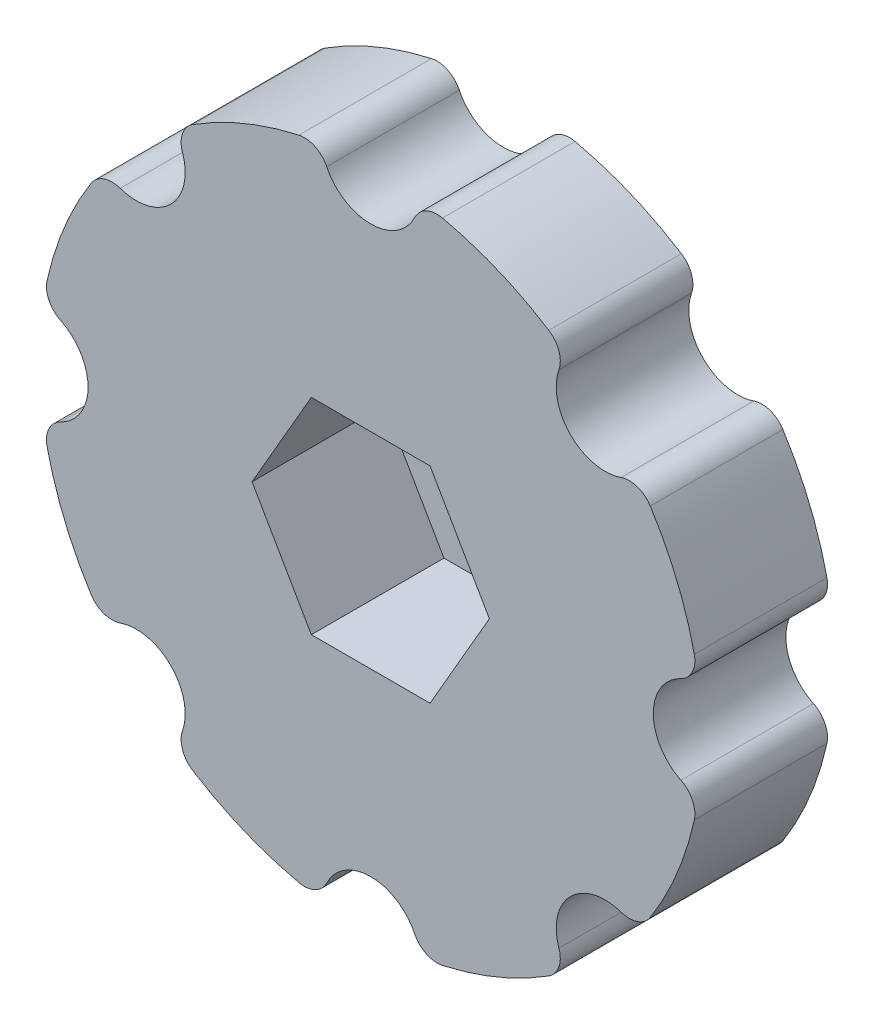
SolidWorks part; units mm, degrees
ref_plane "Alzado" through (0, 0, 0) normal (0, 0, 1) x (1, 0, 0)
ref_plane "Planta" through (0, 0, 0) normal (0, 1, 0) x (1, 0, 0)
ref_plane "Vista lateral" through (0, 0, 0) normal (1, 0, 0) x (0, 0, -1)
sketch "Croquis1" plane through (0, 0, 0) normal (0, 0, 1) x (1, 0, 0)
  line L0 (-1.2042, 1.2) -> (1.2042, 1.2)
  line L2 (-20, 0) -> (20, 0) construction
  line L3 (0, 20) -> (0, -20) construction
  arc A0 (-1.2042, 1.2) -> (1.2042, 1.2) centre (0, 0) ccw
  circle A2 centre (0, 0) radius 20
  dimension "D3" = 40
extrude "Saliente-Extruir1" add sketch "Croquis1" against normal blind 8
sketch "Croquis2" plane through (0, 0, 0) normal (0, 0, 1) x (1, 0, 0)
  circle A0 centre (0, 20) radius 2.75
  circle A1 centre (0, 0) radius 20 construction
  circle A4 centre (14.1424, 14.1428) radius 2.75
  circle A6 centre (20.001, 0.001) radius 2.75
  circle A8 centre (14.1438, -14.1414) radius 2.75
  circle A10 centre (0.002, -20) radius 2.75
  circle A12 centre (-14.1404, -14.1428) radius 2.75
  circle A14 centre (-19.999, -0.001) radius 2.75
  circle A16 centre (-14.1418, 14.1414) radius 2.75
  point P38 (0.001, 0)
  dimension "D1" = 5.5
  dimension "D3" = 15.3073
  dimension "D2" = 8
extrude "Cortar-Extruir1" cut sketch "Croquis2" against normal blind 8
sketch "Croquis3" plane through (0, 0, -8) normal (0, 0, -1) x (-1, 0, 0)
  line L1 (7.1591, 0) -> (3.5796, 6.2)
  line L2 (3.5796, 6.2) -> (-3.5796, 6.2)
  line L3 (-3.5796, 6.2) -> (-7.1591, 0)
  line L4 (-7.1591, 0) -> (-3.5796, -6.2)
  line L5 (-3.5796, -6.2) -> (3.5796, -6.2)
  line L6 (3.5796, -6.2) -> (7.1591, 0)
  circle A0 centre (0, 0) radius 6.2 construction
  dimension "D1" = 12.4
extrude "Cortar-Extruir2" cut sketch "Croquis3" against normal blind 10
sketch "Croquis4" plane through (0, 0, -8) normal (0, 0, -1) x (-1, 0, 0)
  circle A0 centre (0, 0) radius 2.15
  circle A1 centre (0, 0) radius 10
  dimension "D1" = 4.3
  dimension "D2" = 20
extrude "Saliente-Extruir2" add sketch "Croquis4" along normal blind 3
fillet "Redondeo1" radius 10 1 edges at (10, 0, -8)
fillet "Redondeo2" radius 10 1 edges at (-10, 0, -11)
sketch "Croquis5" plane through (0, 0, 0) normal (0, 0, 1) x (1, 0, 0)
  circle A0 centre (0, 20) radius 2.95
  arc A1 (-2.7435, 19.8109) -> (2.7435, 19.8109) centre (0, 20) ccw construction
  circle A2 centre (14.1421, 14.1421) radius 2.95
  circle A3 centre (20, 0) radius 2.95
  circle A4 centre (14.1421, -14.1421) radius 2.95
  circle A5 centre (0, -20) radius 2.95
  circle A6 centre (-14.1421, -14.1421) radius 2.95
  circle A7 centre (-20, 0) radius 2.95
  circle A8 centre (-14.1421, 14.1421) radius 2.95
  point P23 (0, 0)
  dimension "D1" = 0.2
  dimension "D3" = 5.9
  dimension "D2" = 8
extrude "Cortar-Extruir4" cut sketch "Croquis5" against normal through all
fillet "Redondeo4" radius 1.5 16 edges at (-11.908, 16.0686, -4) (-16.0686, 11.908, -4) (-19.7824, -2.942, -4) (-19.7824, 2.942, -4) (-16.0686, -11.908, -4) (-11.908, -16.0686, -4) (2.942, -19.7824, -4) (-2.942, -19.7824, -4) (11.908, -16.0686, -4) (16.0686, -11.908, -4) (19.7824, 2.942, -4) (19.7824, -2.942, -4) (11.908, 16.0686, -4) (16.0686, 11.908, -4) (-2.942, 19.7824, -4) (2.942, 19.7824, -4)
sketch "Croquis6" plane through (0, 0, 0) normal (0, 0, 1) x (1, 0, 0)
  line L0 (0, 2.15) -> (0, -2.15)
  circle A0 centre (0, 0) radius 2.15 construction
sketch "Croquis8" plane through (0, 0, 0) normal (0, 0, 1) x (1, 0, 0)
  circle A0 centre (0, 0) radius 20
